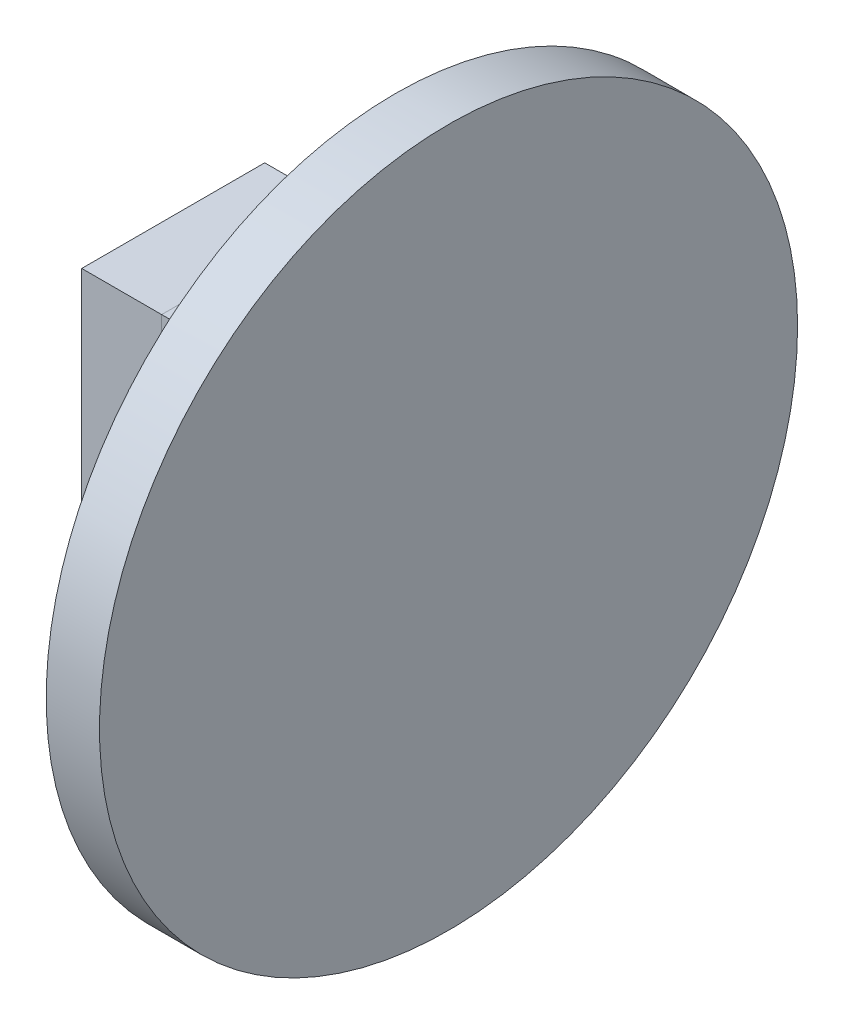
SolidWorks part; units mm, degrees
ref_plane "Front Plane" through (0, 0, 0) normal (0, 0, 1) x (1, 0, 0)
ref_plane "Top Plane" through (0, 0, 0) normal (0, 1, 0) x (1, 0, 0)
ref_plane "Right Plane" through (0, 0, 0) normal (1, 0, 0) x (0, 0, -1)
sketch "Sketch2" plane through (0, 0, 0) normal (1, 0, 0) x (0, 0, -1)
  circle A0 centre (0, 0) radius 19.65
  dimension "D1" = 39.3
extrude "Boss-Extrude1" add sketch "Sketch2" along normal blind 3
sketch "Sketch3" plane through (0, 0, 0) normal (0, 0, 1) x (1, 0, 0)
  line L0 (0, 19.65) -> (0, -19.65) construction
  line L1 (0, 7.45) -> (-12.5, 7.45)
  line L2 (0, 7.45) -> (0, -7.45)
  line L3 (0, -7.45) -> (-12.5, -7.45)
  line L4 (-12.5, 7.45) -> (-12.5, -7.45)
  point P6 (0, 0)
  dimension "D1" = 14.9
  dimension "D2" = 12.5
extrude "Boss-Extrude2" add sketch "Sketch3" along normal mid plane 10.3
sketch "Sketch4" plane through (-12.5, 0, 0) normal (-1, 0, 0) x (0, 0, 1)
  line L0 (5.15, 7.45) -> (-5.15, 7.45) construction
  line L1 (-3.7, 6.3) -> (3.7, 6.3)
  line L2 (-3.7, 6.3) -> (-3.7, -6.3)
  line L3 (-3.7, -6.3) -> (3.7, -6.3)
  line L4 (3.7, 6.3) -> (3.7, -6.3)
  line L5 (5.15, -7.45) -> (5.15, 7.45) construction
  point P4 (0, 6.3)
  point P7 (0, 7.45)
  point P8 (3.7, 0)
  point P11 (5.15, 0)
  dimension "D1" = 7.4
  dimension "D2" = 12.6
extrude "Cut-Extrude1" cut sketch "Sketch4" against normal blind 12.5
fillet "Fillet1" radius 8 4 edges at (0, 7.45, 0) (0, 0, 5.15) (0, -7.45, 0) (0, 0, -5.15) conic rho 0.5
